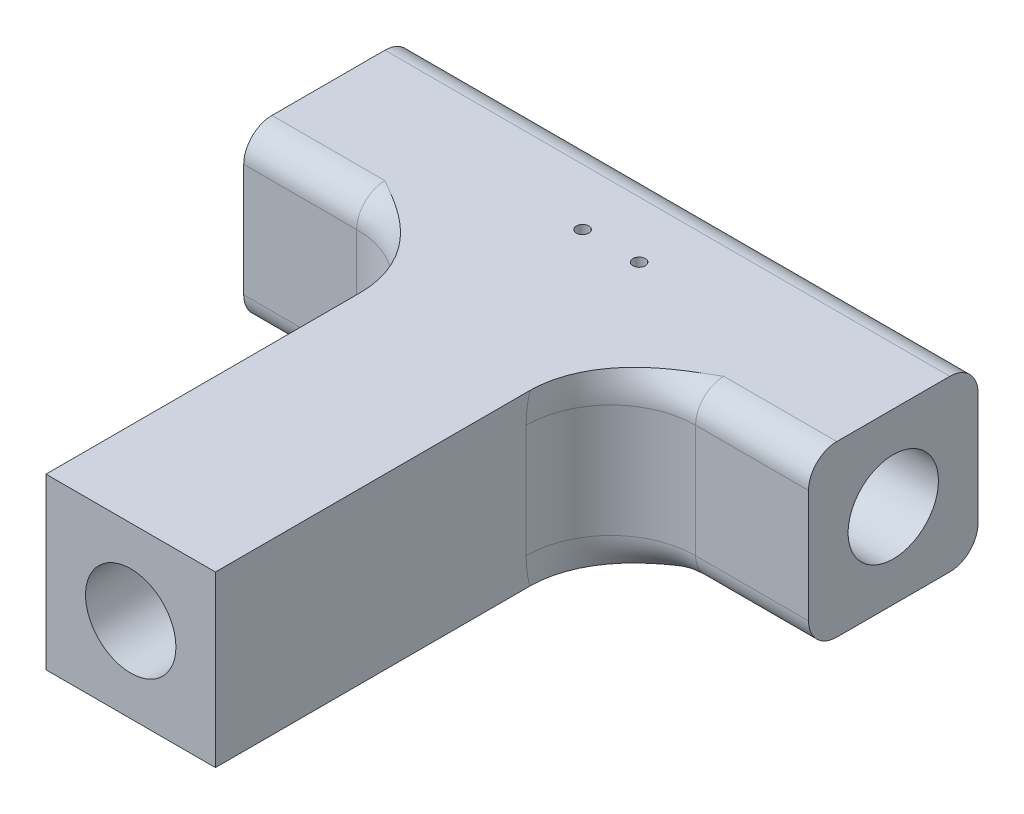
SolidWorks part; units mm, degrees
ref_plane "Front Plane" through (0, 0, 0) normal (0, 0, 1) x (1, 0, 0)
ref_plane "Top Plane" through (0, 0, 0) normal (0, 1, 0) x (1, 0, 0)
ref_plane "Right Plane" through (0, 0, 0) normal (1, 0, 0) x (0, 0, -1)
sketch "Sketch1" plane through (0, 0, 0) normal (0, 1, 0) x (1, 0, 0)
  line L3 (-5, -1.5) -> (5, -1.5)
  line L4 (-5, -1.5) -> (-5, 1.5)
  line L5 (-5, 1.5) -> (5, 1.5)
  line L6 (5, -1.5) -> (5, 1.5)
  line L7 (-5, -1.5) -> (5, 1.5) construction
  line L8 (-5, 1.5) -> (5, -1.5) construction
  point P0 (0, 0)
  dimension "D1" = 10
  dimension "D2" = 3
extrude "Boss-Extrude1" add sketch "Sketch1" along normal blind 3
sketch "Sketch2" plane through (0, 3, 0) normal (0, 1, 0) x (1, 0, 0)
  line L0 (-55, 0) -> (55, 0) construction
  point P0 (0.5, 0)
  point P1 (-0.5, 0)
  dimension "D1" = 1
  dimension "D2" = 0.5
sketch "Sketch6" plane through (-5, 0, 0) normal (-1, 0, 0) x (0, 0, 1)
  line L0 (0, -55) -> (0, 55) construction
  line L1 (-1.5, 3) -> (1.5, 3) construction
  point P0 (0, 1.5)
  point P1 (0, 0)
  dimension "D1" = 1.5
hole_wizard "#90 (0.0087) Diameter Hole1" positions "Sketch9" profile "Sketch10" hole size "#90" standard "ANSI Inch" end condition through all
sketch "Sketch9" plane through (0, 3, 0) normal (0, 1, 0) x (1, 0, 0)
  point P0 (0.5, 0)
  point P3 (-0.5, 0)
sketch "Sketch10" plane through (0.5, 3, 0) normal (1, 0, 0) x (0, 0, 1)
  line L0 (0, 0) -> (0, 3)
  line L1 (0, 3) -> (0.1105, 3)
  line L2 (0.1105, 3) -> (0.1105, 0)
  line L5 (0.1105, 0) -> (0, 0)
  line L11 (0, -6.35) -> (0, 107.95) construction
  dimension "Thru Hole Dia." = 0.221
  dimension "Thru Hole Depth" = 3
hole_wizard "Tap Drill for M2x0.4 Tap1" positions "Sketch7" profile "Sketch8" hole size "M2x0.4" standard "ANSI Metric"
sketch "Sketch7" plane through (-5, 0, 0) normal (-1, 0, 0) x (0, 0, 1)
  point P0 (0, 1.5)
sketch "Sketch8" plane through (-5, 1.5, 0) normal (0, 1, 0) x (0, 0, 1)
  line L0 (0, 0) -> (0, 4.85)
  line L1 (0, 4.85) -> (0.8, 4.3693)
  line L2 (0.8, 4.3693) -> (0.8, 0)
  line L5 (0.8, 0) -> (0, 0)
  line L10 (0, 4.85) -> (-0.8, 4.3693) construction
  line L11 (0, -6.35) -> (0, 107.95) construction
  dimension "Hole Dia." = 1.6
  dimension "Hole Depth" = 4.85
  dimension "Drill Angle" = 118
mirror "Mirror1" about plane through (0, 0, 0) normal (1, 0, 0) of "Tap Drill for M2x0.4 Tap1"
sketch "Sketch15" plane through (0, 0, 1.5) normal (0, 0, 1) x (1, 0, 0)
  line L0 (0, -1.65) -> (0, 1.65) construction
  line L1 (-1.5, 0) -> (1.5, 0)
  line L2 (-1.5, 0) -> (-1.5, 3)
  line L3 (-1.5, 3) -> (1.5, 3)
  line L4 (1.5, 0) -> (1.5, 3)
  line L5 (-1.5, 0) -> (1.5, 3) construction
  line L6 (-1.5, 3) -> (1.5, 0) construction
  line L7 (-5, 3) -> (5, 3) construction
  point P0 (0, 1.5)
  point P5 (0, 0)
  dimension "D1" = 3
  dimension "D2" = 3
extrude "Boss-Extrude2" add sketch "Sketch15" along normal blind 7
sketch "Sketch16" plane through (0, 0, 8.5) normal (0, 0, 1) x (1, 0, 0)
  line L0 (0, -1.65) -> (0, 1.65) construction
  line L1 (1.5, 3) -> (-1.5, 3) construction
  point P0 (0, 1.5)
  point P1 (0, 0)
  dimension "D1" = 1.5
hole_wizard "M2x0.4 Tapped Hole1" positions "Sketch17" profile "Sketch18" tap size "M2x0.4" standard "ANSI Metric"
sketch "Sketch17" plane through (0, 0, 8.5) normal (0, 0, 1) x (1, 0, 0)
  point P0 (0, 1.5)
sketch "Sketch18" plane through (0, 1.5, 8.5) normal (1, 0, 0) x (0, -1, 0)
  line L0 (0, 0) -> (0, 5.4807)
  line L1 (0, 5.4807) -> (0.8, 5)
  line L2 (0.8, 5) -> (0.8, 0)
  line L5 (0.8, 0) -> (0, 0)
  line L10 (0, 5.4807) -> (-0.8, 5) construction
  line L11 (0, -6.35) -> (0, 107.95) construction
  dimension "Tap Drill Dia." = 1.6
  dimension "Tap Drill Depth" = 5
  dimension "Drill Angle" = 118
cosmetic thread "Hole Thread1" parameters "D1"=4, "D2"=2
fillet "Fillet4" radius 0.5 6 edges at (3.25, 3, 1.5) (3.25, 0, 1.5) (-3.25, 0, 1.5) (0, 0, -1.5) (0, 3, -1.5) (-3.25, 3, 1.5)
fillet "Fillet3" radius 1.5 6 edges at (-1.5, 1.5, 1.5) (1.5, 1.5, 1.5) (-1.5, 2.8536, 1.3536) (-1.5, 0.1464, 1.3536) (1.5, 0.1464, 1.3536) (1.5, 2.8536, 1.3536)
